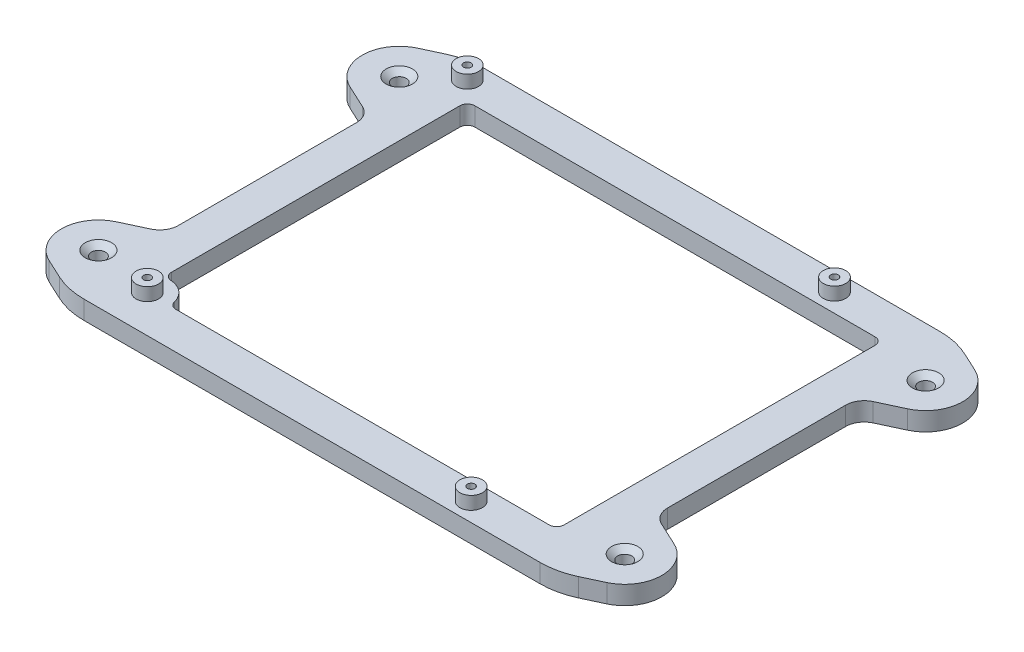
SolidWorks part; units mm, degrees
ref_plane "Front Plane" through (0, 0, 0) normal (0, 0, 1) x (1, 0, 0)
ref_plane "Top Plane" through (0, 0, 0) normal (0, 1, 0) x (1, 0, 0)
ref_plane "Right Plane" through (0, 0, 0) normal (1, 0, 0) x (0, 0, -1)
sketch "Quarter Base Sketch" plane through (0, 0, 0) normal (0, 1, 0) x (1, 0, 0)
  line L0 (0, 0) -> (0, 89.76) construction
  line L1 (0, 0) -> (-118.272, 0) construction
  line L2 (0, 53.955) -> (-66, 53.955)
  line L3 (-66, 53.955) -> (-75.2262, 49.6528)
  line L4 (-75.2262, 31.5266) -> (-66, 27.2244)
  line L5 (-66, 27.2244) -> (-66, 0)
  line L6 (-71, 40.5897) -> (-28.7156, 40.5897) construction
  line L7 (-66, 0) -> (-56, 0)
  line L8 (0, 43.955) -> (0, 53.955)
  line L9 (0, 43.955) -> (-56, 43.955)
  line L10 (-56, 43.955) -> (-56, 0)
  arc A0 (-75.2262, 49.6528) -> (-75.2262, 31.5266) centre (-71, 40.5897) ccw
  dimension "D2" = 10
  dimension "D1" = 132
  dimension "D3" = 25
  dimension "D4" = 5
  dimension "D5" = 107.91
  dimension "D6" = 10
  dimension "D7" = 10
extrude "Quarter Base" add sketch "Quarter Base Sketch" along normal blind 5
mirror "Base Mirror 1" about plane through (-66, 5, 0) normal (0, 0, -1) of bodies 101
mirror "Base Mirror 2" about plane through (0, 5, -43.955) normal (-1, 0, 0) of bodies 102
sketch "Corner Screw Expansion Sketch" plane through (0, 5, 0) normal (0, 1, 0) x (1, 0, 0)
  line L0 (66, -53.955) -> (-66, -53.955) construction
  circle A0 centre (-54.523, -43.876) radius 6.025
  point P2 (-63.667, -52.745)
  point P3 (38.06, 48.955)
  point P8 (-61, 48.955)
  point P9 (37.933, -48.955)
  dimension "D1" = 12.05
  dimension "D2" = 10.079
  dimension "D3" = 54.523
  dimension "D4" = 9.144
  dimension "D5" = 8.869
  dimension "D6" = 2.667
  dimension "D7" = 101.7
  dimension "D8" = 3.79
  dimension "D9" = 101.6
  dimension "D10" = 101.727
extrude "Corner Screw Expansion" add sketch "Corner Screw Expansion Sketch" against normal up to surface (5 mm away) up to face at (0, 0, 0)
sketch "Standoffs Extrusion Sketch" plane through (0, 5, 0) normal (0, 1, 0) x (1, 0, 0)
  circle A0 centre (-61, 48.955) radius 3.025
  circle A1 centre (-54.523, -43.876) radius 3.025
  circle A2 centre (37.933, -48.955) radius 3.025
  circle A3 centre (38.06, 48.955) radius 3.025
  dimension "D1" = 6.05
extrude "Standoffs Extrusion" add sketch "Standoffs Extrusion Sketch" along normal blind 3.5
sketch "Smoothieboard Screw Holes Sketch" plane through (0, 8.5, 0) normal (0, 1, 0) x (1, 0, 0)
  circle A0 centre (-54.523, -43.876) radius 1.025
  circle A1 centre (37.933, -48.955) radius 1.025
  circle A2 centre (38.06, 48.955) radius 1.025
  circle A3 centre (-61, 48.955) radius 1.025
  dimension "D1" = 2.05
extrude "Smoothieboard Screw Holes" cut sketch "Smoothieboard Screw Holes Sketch" against normal through all
hole_wizard "No. 6 Mounting Screws" positions "No. 6 Mounting Screws Position Sketch" profile "No. 6 Mounting Screws Profile Sketch" countersink size "#6" standard "ANSI Inch" end condition up to next
sketch3d "No. 6 Mounting Screws Position Sketch"
  arc A0 (75.2262, 5, -49.6528) -> (75.2262, 5, -31.5266) centre (71, 5, -40.5897) ccw construction
  arc A1 (75.2262, 5, 49.6528) -> (75.2262, 5, 31.5266) centre (71, 5, 40.5897) ccw construction
  arc A2 (-75.2262, 5, 49.6528) -> (-75.2262, 5, 31.5266) centre (-71, 5, 40.5897) ccw construction
  arc A3 (-75.2262, 5, -49.6528) -> (-75.2262, 5, -31.5266) centre (-71, 5, -40.5897) ccw construction
  point P0 (-71, 5, -40.5897)
  point P2 (-71, 5, 40.5897)
  point P4 (71, 5, 40.5897)
  point P6 (71, 5, -40.5897)
  point P11 (71, -5, -40.5897)
  point P15 (71, 15, 40.5897)
  point P19 (-71, -5, 40.5897)
  point P23 (-71, 15, -40.5897)
sketch "No. 6 Mounting Screws Profile Sketch" plane through (-71, 5, -40.5897) normal (1, 0, 0) x (0, 0, 1)
  line L0 (0, 0) -> (0, 5)
  line L1 (0, 5) -> (1.8986, 5)
  line L2 (1.8986, 5) -> (1.8986, 1.38)
  line L3 (1.8986, 1.38) -> (3.5433, 0)
  line L5 (3.5433, 0) -> (0, 0)
  line L6 (-1.8986, 1.38) -> (-3.5433, 0) construction
  line L11 (0, -6.35) -> (0, 107.95) construction
  dimension "Thru Hole Dia." = 3.7973
  dimension "Thru Hole Depth" = 5
  dimension "Near C'Sink Dia." = 7.0866
  dimension "Near C'Sink Angle" = 100
fillet "Inside Corner Fillets" radius 2 5 edges at (-56, 2.5, 38.0348) (-48.4985, 2.5, 43.955) (56, 2.5, 43.955) (56, 2.5, -43.955) (-56, 2.5, -43.955)
fillet "Outside Corner Fillets 1" radius 5 4 edges at (-66, 2.5, 27.2244) (-66, 2.5, -27.2244) (66, 2.5, -27.2244) (66, 2.5, 27.2244)
fillet "Outside Corner Fillets 2" radius 20 4 edges at (66, 2.5, -53.955) (66, 2.5, 53.955) (-66, 2.5, 53.955) (-66, 2.5, -53.955)
